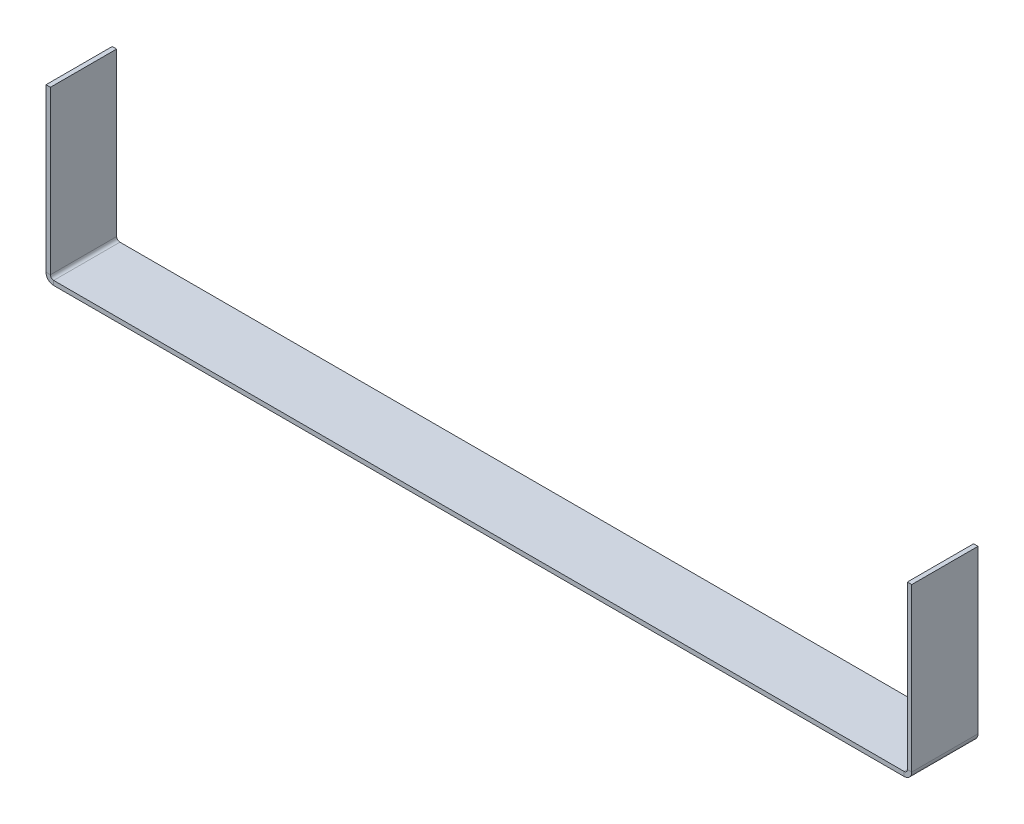
SolidWorks part; units mm, degrees
note: The reader was unsure of these and kept them because the rebuilt part matched: flange length of "Ребро-кромка1", "Ребро-кромка2".
material "Простая углеродистая сталь"
ref_plane "Спереди" through (0, 0, 0) normal (0, 0, 1) x (1, 0, 0)
ref_plane "Сверху" through (0, 0, 0) normal (0, 1, 0) x (1, 0, 0)
ref_plane "Справа" through (0, 0, 0) normal (1, 0, 0) x (0, 0, -1)
sketch "Эскиз1" plane through (0, 0, 0) normal (0, 1, 0) x (1, 0, 0)
  line L1 (0, 0) -> (196, 0)
  line L2 (0, 0) -> (0, 15)
  line L3 (0, 15) -> (196, 15)
  line L4 (196, 0) -> (196, 15)
  circle A0 centre (99, 7.5) radius 2
  circle A1 centre (169, 7.5) radius 2
  circle A2 centre (28, 7.5) radius 2
  dimension "D3" = 2
  dimension "D1" = 196
  dimension "D2" = 15
  dimension "D4" = 2
base flange "Базовая кромка1" sketch "Эскиз1" thickness 1 reverse thickness direction no parameters "D1"=0.7366
edge flange "Ребро-кромка1" sketch "Эскиз8" flange angle 90 flange length 38.5 flange position material inside bend radius 0.7366 thickness 1 relief rectangular parameters "D6"=10
sketch "Эскиз8" plane through (0, 0, 0) normal (-1, 0, 0) x (0, 0, 1)
  line L0 (-15, 0) -> (0, 0) construction
  line L1 (-15, 0) -> (0, 0)
  line L2 (-15, 0) -> (-15, 37.5)
  line L3 (-15, 37.5) -> (0, 37.5)
  line L4 (0, 37.5) -> (0, 0)
bend "EdgeBend1" bend radius 0.7366 bend angle 90 parameters "D5"=1
edge flange "Ребро-кромка2" sketch "Эскиз11" flange angle 90 flange length 38.5 flange position material inside bend radius 0.7366 thickness 1 relief rectangular parameters "D6"=10
sketch "Эскиз11" plane through (196, 0, 0) normal (1, 0, 0) x (0, 0, -1)
  line L2 (0, 0) -> (0, 37.5)
  line L3 (0, 37.5) -> (15, 37.5)
  line L4 (15, 37.5) -> (15, 0)
  line L5 (0, 0) -> (15, 0) construction
  line L6 (0, 0) -> (15, 0)
bend "EdgeBend2" bend radius 0.7366 bend angle 90 parameters "D5"=2
sketch "Сгиб-Линии1" [suppressed] plane through (0, 0, 0) normal (0, 1, 0) x (1, 0, 0)
sketch "Граничная рамка1" [suppressed] plane through (0, 0, 0) normal (0, 1, 0) x (1, 0, 0)
sheet metal parameters "Листовой металл4" thickness 1 parameters "D1"=0.7366
flat pattern "Развертка4" [suppressed]
sketch "Сгиб-Линии2" plane through (0, 0, 0) normal (0, 1, 0) x (1, 0, 0)
sketch3d "Граничная рамка2" [suppressed]
  line L0 (150, 15, 0) -> (0, 15, 0) construction
  line L1 (150, 0, 0) -> (0, 0, 0) construction
  line L2 (150, 15, 0) -> (150, 0, 0) construction
  line L3 (0, 15, 0) -> (0, 0, 0) construction
sheet metal parameters "Листовой металл5" thickness 1 parameters "D1"=0.7366
flat pattern "Развертка4" [suppressed]
sketch "Сгиб-Линии2" plane through (0, 0, 0) normal (0, 1, 0) x (1, 0, 0)
sketch3d "Граничная рамка2" [suppressed]
  line L0 (150, 15, 0) -> (0, 15, 0) construction
  line L1 (150, 0, 0) -> (0, 0, 0) construction
  line L2 (150, 15, 0) -> (150, 0, 0) construction
  line L3 (0, 15, 0) -> (0, 0, 0) construction
bend of the flat pattern "Плоское состояние-<EdgeBend1>1"
sheet metal parameters "Листовой металл6" thickness 1 parameters "D1"=0.7366
flat pattern "Развертка4" [suppressed]
sketch "Сгиб-Линии2" plane through (0, 0, 0) normal (0, 1, 0) x (1, 0, 0)
sketch3d "Граничная рамка2" [suppressed]
  line L0 (150, 15, 0) -> (0, 15, 0) construction
  line L1 (150, 0, 0) -> (0, 0, 0) construction
  line L2 (150, 15, 0) -> (150, 0, 0) construction
  line L3 (0, 15, 0) -> (0, 0, 0) construction
bend of the flat pattern "Плоское состояние-<EdgeBend1>1"
bend of the flat pattern "Плоское состояние-<EdgeBend2>1"
